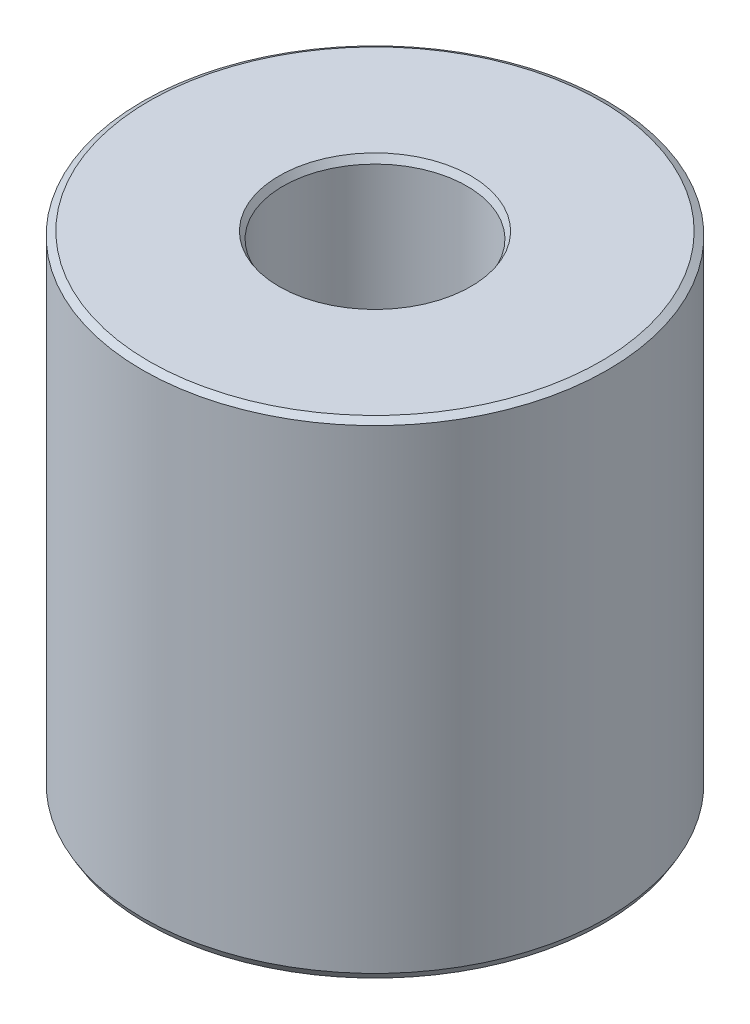
SolidWorks part; units mm, degrees
ref_plane "Front Plane" through (0, 0, 0) normal (0, 0, 1) x (1, 0, 0)
ref_plane "Top Plane" through (0, 0, 0) normal (0, 1, 0) x (1, 0, 0)
ref_plane "Right Plane" through (0, 0, 0) normal (1, 0, 0) x (0, 0, -1)
sketch "Sketch1" plane through (0, 0, 0) normal (0, 1, 0) x (1, 0, 0)
  circle A0 centre (0, 0) radius 50
  dimension "SLEEVE_OD" = 100
extrude "Boss-Extrude1" add sketch "Sketch1" along normal blind 104.3196
sketch "Sketch2" plane through (0, 0, 0) normal (0, 1, 0) x (1, 0, 0)
  circle A0 centre (0, 0) radius 19.7639
  dimension "BORE_D" = 39.5279
extrude "Cut-Extrude1" cut sketch "Sketch2" along normal through all
chamfer "Chamfer1" distance 0.8539 angle 60 4 edges at (0, 104.3196, 19.7639) (0, 0, 19.7639) (0, 0, 50) (0, 104.3196, 50) first distance on face at (0, 104.3196, 19.7639) first distance on face at (0, 0, 19.7639) first distance on face at (0, 104.3196, 50)
